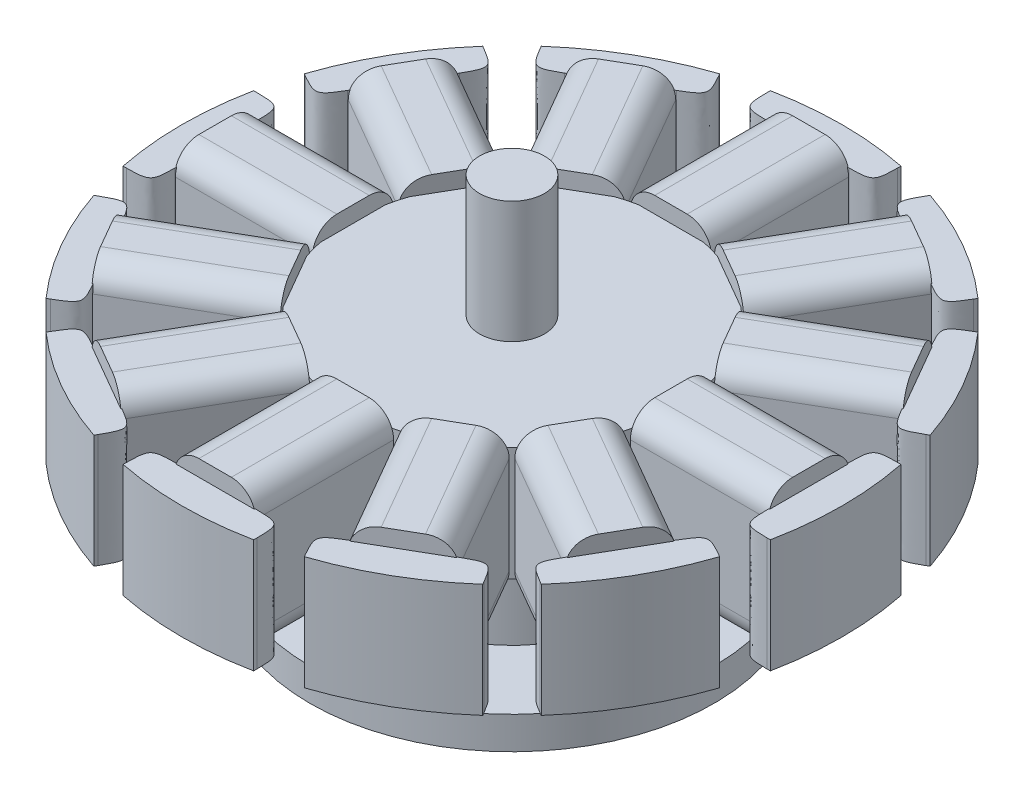
SolidWorks part; units mm, degrees
material "Литая легированная сталь"
ref_plane "Спереди" through (0, 0, 0) normal (0, 0, 1) x (1, 0, 0)
ref_plane "Сверху" through (0, 0, 0) normal (0, 1, 0) x (1, 0, 0)
ref_plane "Справа" through (0, 0, 0) normal (1, 0, 0) x (0, 0, -1)
other "Configuration Table"
sketch "Эскиз1" plane through (0, 0, 0) normal (0, 1, 0) x (1, 0, 0)
  circle A0 centre (0, 0) radius 10
  dimension "D1" = 20
extrude "Подшипник" add sketch "Эскиз1" along normal blind 7
sketch "Эскиз2" plane through (0, 0, 0) normal (0, 1, 0) x (1, 0, 0)
  circle A0 centre (0, 0) radius 7.25
  dimension "D1" = 14.5
extrude "Нижняя втулка" add sketch "Эскиз2" against normal blind 7.5
sketch "Эскиз3" plane through (0, 0, 0) normal (0, 1, 0) x (1, 0, 0)
  circle A0 centre (0, 0) radius 12.45
  dimension "D1" = 24.9
extrude "Нижний фланец" add sketch "Эскиз3" along normal blind 2 from surface starting at face at (0, -7.5, 7.25)
sketch "Эскиз4" plane through (0, 0, 0) normal (0, 1, 0) x (1, 0, 0)
  line L0 (0, 9.5) -> (0, -9.5) construction
  line L1 (-8, 0) -> (8, 0) construction
  circle A0 centre (-8, 0) radius 1.5
  circle A1 centre (0, -9.5) radius 1.5
  circle A2 centre (8, 0) radius 1.5
  circle A3 centre (0, 9.5) radius 1.5
  point P5 (0, 0)
  point P9 (0, 0)
  dimension "D3" = 3
  dimension "D1" = 16
  dimension "D2" = 19
extrude "Монтажные отверстия на фланце" cut sketch "Эскиз4" against normal through all
sketch "Эскиз5" plane through (0, 0, 0) normal (0, 1, 0) x (1, 0, 0)
  circle A0 centre (0, 0) radius 2
  dimension "D1" = 4
extrude "Вал" add sketch "Эскиз5" along normal blind 24 from offset 9.5 offset against normal yes
chamfer "Фаска1" distance 0.5 angle 45 1 edges at (0, -9.5, 2)
sketch "Эскиз6" plane through (0, 0, 0) normal (0, 1, 0) x (1, 0, 0)
  line L0 (0, 0) -> (0, 14.023) construction
  line L1 (-4.025, 19.948) -> (-4.025, 18.248)
  line L2 (2, 18.248) -> (-2, 18.248)
  line L3 (2, 18.248) -> (2, 9.798)
  line L4 (2, 9.798) -> (-2, 9.798)
  line L5 (-2, 18.248) -> (-2, 9.798)
  line L6 (0, 9.798) -> (0, 18.248) construction
  line L7 (2, 14.023) -> (-2, 14.023) construction
  line L8 (-4.025, 18.248) -> (-2, 18.248)
  line L13 (2, 18.248) -> (4.025, 18.248)
  line L14 (4.025, 18.248) -> (4.025, 19.948)
  line L15 (10.856, 14.8032) -> (6.631, 7.4853)
  line L16 (6.631, 7.4853) -> (3.1669, 9.4853)
  line L17 (7.3919, 16.8032) -> (3.1669, 9.4853)
  line L18 (5.6382, 17.8157) -> (7.3919, 16.8032)
  line L19 (6.4882, 19.288) -> (5.6382, 17.8157)
  line L20 (12.6097, 13.7907) -> (13.4597, 15.263)
  line L21 (10.856, 14.8032) -> (12.6097, 13.7907)
  line L22 (16.8032, 7.3919) -> (9.4853, 3.1669)
  line L23 (9.4853, 3.1669) -> (7.4853, 6.631)
  line L24 (14.8032, 10.856) -> (7.4853, 6.631)
  line L25 (13.7907, 12.6097) -> (14.8032, 10.856)
  line L26 (15.263, 13.4597) -> (13.7907, 12.6097)
  line L27 (17.8157, 5.6382) -> (19.288, 6.4882)
  line L28 (16.8032, 7.3919) -> (17.8157, 5.6382)
  line L29 (18.248, -2) -> (9.798, -2)
  line L30 (9.798, -2) -> (9.798, 2)
  line L31 (18.248, 2) -> (9.798, 2)
  line L32 (18.248, 4.025) -> (18.248, 2)
  line L33 (19.948, 4.025) -> (18.248, 4.025)
  line L34 (18.248, -4.025) -> (19.948, -4.025)
  line L35 (18.248, -2) -> (18.248, -4.025)
  line L36 (14.8032, -10.856) -> (7.4853, -6.631)
  line L37 (7.4853, -6.631) -> (9.4853, -3.1669)
  line L38 (16.8032, -7.3919) -> (9.4853, -3.1669)
  line L39 (17.8157, -5.6382) -> (16.8032, -7.3919)
  line L40 (19.288, -6.4882) -> (17.8157, -5.6382)
  line L41 (13.7907, -12.6097) -> (15.263, -13.4597)
  line L42 (14.8032, -10.856) -> (13.7907, -12.6097)
  line L43 (7.3919, -16.8032) -> (3.1669, -9.4853)
  line L44 (3.1669, -9.4853) -> (6.631, -7.4853)
  line L45 (10.856, -14.8032) -> (6.631, -7.4853)
  line L46 (12.6097, -13.7907) -> (10.856, -14.8032)
  line L47 (13.4597, -15.263) -> (12.6097, -13.7907)
  line L48 (5.6382, -17.8157) -> (6.4882, -19.288)
  line L49 (7.3919, -16.8032) -> (5.6382, -17.8157)
  line L50 (-2, -18.248) -> (-2, -9.798)
  line L51 (-2, -9.798) -> (2, -9.798)
  line L52 (2, -18.248) -> (2, -9.798)
  line L53 (4.025, -18.248) -> (2, -18.248)
  line L54 (4.025, -19.948) -> (4.025, -18.248)
  line L55 (-4.025, -18.248) -> (-4.025, -19.948)
  line L56 (-2, -18.248) -> (-4.025, -18.248)
  line L57 (-10.856, -14.8032) -> (-6.631, -7.4853)
  line L58 (-6.631, -7.4853) -> (-3.1669, -9.4853)
  line L59 (-7.3919, -16.8032) -> (-3.1669, -9.4853)
  line L60 (-5.6382, -17.8157) -> (-7.3919, -16.8032)
  line L61 (-6.4882, -19.288) -> (-5.6382, -17.8157)
  line L62 (-12.6097, -13.7907) -> (-13.4597, -15.263)
  line L63 (-10.856, -14.8032) -> (-12.6097, -13.7907)
  line L64 (-16.8032, -7.3919) -> (-9.4853, -3.1669)
  line L65 (-9.4853, -3.1669) -> (-7.4853, -6.631)
  line L66 (-14.8032, -10.856) -> (-7.4853, -6.631)
  line L67 (-13.7907, -12.6097) -> (-14.8032, -10.856)
  line L68 (-15.263, -13.4597) -> (-13.7907, -12.6097)
  line L69 (-17.8157, -5.6382) -> (-19.288, -6.4882)
  line L70 (-16.8032, -7.3919) -> (-17.8157, -5.6382)
  line L71 (-18.248, 2) -> (-9.798, 2)
  line L72 (-9.798, 2) -> (-9.798, -2)
  line L73 (-18.248, -2) -> (-9.798, -2)
  line L74 (-18.248, -4.025) -> (-18.248, -2)
  line L75 (-19.948, -4.025) -> (-18.248, -4.025)
  line L76 (-18.248, 4.025) -> (-19.948, 4.025)
  line L77 (-18.248, 2) -> (-18.248, 4.025)
  line L78 (-14.8032, 10.856) -> (-7.4853, 6.631)
  line L79 (-7.4853, 6.631) -> (-9.4853, 3.1669)
  line L80 (-16.8032, 7.3919) -> (-9.4853, 3.1669)
  line L81 (-17.8157, 5.6382) -> (-16.8032, 7.3919)
  line L82 (-19.288, 6.4882) -> (-17.8157, 5.6382)
  line L83 (-13.7907, 12.6097) -> (-15.263, 13.4597)
  line L84 (-14.8032, 10.856) -> (-13.7907, 12.6097)
  line L85 (-7.3919, 16.8032) -> (-3.1669, 9.4853)
  line L86 (-3.1669, 9.4853) -> (-6.631, 7.4853)
  line L87 (-10.856, 14.8032) -> (-6.631, 7.4853)
  line L88 (-12.6097, 13.7907) -> (-10.856, 14.8032)
  line L89 (-13.4597, 15.263) -> (-12.6097, 13.7907)
  line L90 (-5.6382, 17.8157) -> (-6.4882, 19.288)
  line L91 (-7.3919, 16.8032) -> (-5.6382, 17.8157)
  circle A0 centre (0, 0) radius 10 construction
  arc A1 (4.025, 19.948) -> (-4.025, 19.948) centre (0, 0) ccw
  arc A2 (13.4597, 15.263) -> (6.4882, 19.288) centre (0, 0) ccw
  arc A3 (19.288, 6.4882) -> (15.263, 13.4597) centre (0, 0) ccw
  arc A4 (19.948, -4.025) -> (19.948, 4.025) centre (0, 0) ccw
  arc A5 (15.263, -13.4597) -> (19.288, -6.4882) centre (0, 0) ccw
  arc A6 (6.4882, -19.288) -> (13.4597, -15.263) centre (0, 0) ccw
  arc A7 (-4.025, -19.948) -> (4.025, -19.948) centre (0, 0) ccw
  arc A8 (-13.4597, -15.263) -> (-6.4882, -19.288) centre (0, 0) ccw
  arc A9 (-19.288, -6.4882) -> (-15.263, -13.4597) centre (0, 0) ccw
  arc A10 (-19.948, 4.025) -> (-19.948, -4.025) centre (0, 0) ccw
  arc A11 (-15.263, 13.4597) -> (-19.288, 6.4882) centre (0, 0) ccw
  arc A12 (-6.4882, 19.288) -> (-13.4597, 15.263) centre (0, 0) ccw
  point P104 (0, 0)
  dimension "D2" = 20.35
  dimension "D1" = 4
  dimension "D3" = 8.05
  dimension "D4" = 1.7
  dimension "D5" = 12
extrude "Сердечники катушек" add sketch "Эскиз6" along normal up to surface (7 mm away) contours L14 A1 L1 L8 L2 L13 | L2 L5 L4 L3 | L20 A2 L19 L18 L17 L16 L15 L21 | L27 A3 L26 L25 L24 L23 L22 L28 | L34 A4 L33 L32 L31 L30 L29 L35 | L41 A5 L40 L39 L38 L37 L36 L42 | L48 A6 L47 L46 L45 L44 L43 L49 | L55 A7 L54 L53 L52 L51 L50 L56 | L62 A8 L61 L60 L59 L58 L57 L63 | L69 A9 L68 L67 L66 L65 L64 L70 | L76 A10 L75 L74 L73 L72 L71 L77 | L83 A11 L82 L81 L80 L79 L78 L84 | L90 A12 L89 L88 L87 L86 L85 L91 region at (0, 0, -19.2359) region at (0, 0, -14.023) region at (7.8434, 0, -13.5852) region at (13.5852, 0, -7.8434) region at (15.6869, 0, 0) region at (13.5852, 0, 7.8434) region at (7.8434, 0, 13.5852) region at (0, 0, 15.6869) region at (-7.8434, 0, 13.5852) region at (-13.5852, 0, 7.8434) region at (-15.6869, 0, 0) region at (-13.5852, 0, -7.8434) region at (-7.8434, 0, -13.5852) up to face at (0, 7, 2)
sketch "Эскиз8" plane through (0, 0, 0) normal (0, 0, 1) x (1, 0, 0)
  line L0 (0, 0) -> (0, 7) construction
  line L1 (4.025, 7) -> (-4.025, 7) construction
  line L3 (2.5, 8) -> (-2.5, 8)
  line L4 (2.5, 8) -> (2.5, -1)
  line L5 (2.5, -1) -> (-2.5, -1)
  line L6 (-2.5, 8) -> (-2.5, -1)
  line L7 (0, -1) -> (0, 8) construction
  line L8 (2.5, 3.5) -> (-2.5, 3.5) construction
  point P5 (0, 3.5)
  dimension "D1" = 5
  dimension "D2" = 9
extrude "Катушка" add sketch "Эскиз8" along normal blind 8.5 from vertex starting at point (2, 7, 9.798)
fillet "Скругление1" radius 1.5 4 edges at (2.5, -1, 14.048) (-2.5, -1, 14.048) (-2.5, 8, 14.048) (2.5, 8, 14.048)
fillet "Скругление2" radius 1.5 2 edges at (4.025, 3.5, 18.248) (-4.025, 3.5, 18.248) conic rho 0.7
pattern_circular "Круговой массив2" count 12 over 360 about axis through (0, 14.5, 0) along (0, -1, 0) of "Катушка", "Скругление1", "Скругление2"
equation "\"D2@Эскиз6\"=40.7/2"
